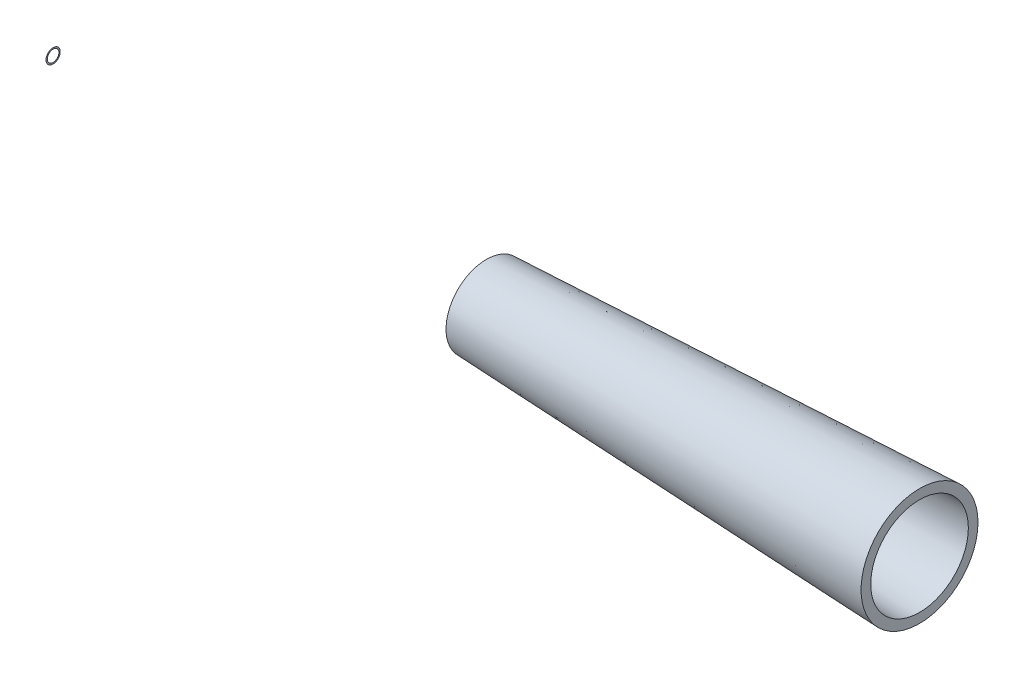
SolidWorks part; units mm, degrees
note: '?' marks a value the reader was unsure of.
ref_plane "Front Plane" through (0, 0, 0) normal (0, 0, 1) x (1, 0, 0)
ref_plane "Top Plane" through (0, 0, 0) normal (0, 1, 0) x (1, 0, 0)
ref_plane "Right Plane" through (0, 0, 0) normal (1, 0, 0) x (0, 0, -1)
sketch "Sketch2" plane through (0, 0, 0) normal (0, 0, 1) x (1, 0, 0)
  line L0 (-19.2758, 0) -> (50, 0) construction
  line L1 (0, 21.4747) -> (0, -15.9358) construction
  line L2 (0, 1.2) -> (54.9325, 5.0413) construction
  line L3 (0, 3.2) -> (55.9028, 7.1091) construction
  line L4 (0, 1.2) -> (50, 4.6963)
  line L5 (1.8511, 3.3294) -> (50, 6.6963)
  line L6 (50, 0) -> (50, 20.2328) construction
  line L7 (50, 6.6963) -> (50, 4.6963)
  arc A0 (0, 1.2) -> (1.8511, 3.3294) centre (1.9903, 1.3392) cw
  dimension "D1" = 4
  dimension "D2" = 1.2
  dimension "D3" = 2
  dimension "D4" = 50
revolve "Revolve2" add sketch "Sketch2" angle 360 about L0
ref_plane "Plane1" through (50, 0, 0) normal (1, 0, 0) x (0, 0, -1)
ref_axis "Axis1" through (50, 0, 0) along (-1, 0, 0)
sketch "Sketch3" plane through (0, 0, 0) normal (0, 0, 1) x (1, 0, 0)
  line L0 (50, 6.6963) -> (180, 6.6963) construction
  line L1 (50, -7.366) -> (50, 7.366) construction
  line L2 (50, 6.6963) -> (1.8511, 3.3294) construction
  line L3 (50, 6.6963) -> (180, 12.145) construction
  line L4 (50, 4.6946) -> (180, 10.1432)
  line L5 (180, 10.1432) -> (180, 12.145)
  line L6 (180, 12.145) -> (50, 6.6963)
  line L7 (50, 6.6963) -> (50, 4.6946)
  dimension "D1" = 2.4
  dimension "D2" = 130
  dimension "D3" = 2
revolve "Revolve3" add sketch "Sketch3" angle 360 about axis through (50, 0, 0) along (-1, 0, 0)
ref_plane "Plane2" through (90, 0, 0) normal (1, 0, 0) x (0, 0, -1)
ref_plane "Plane3" through (180, 0, 0) normal (1, 0, 0) x (0, 0, -1)
ref_plane "Plane4" through (0, -12.145, 0) normal (0, 1, 0) x (1, 0, 0)
ref_axis "Axis2" through (180, -12.145, -13.3595) along (0, 0, 1)?
ref_plane "Plane5" through (83.9275, 83.9275, 0) normal (-0.7071, -0.7071, 0) x (0, 0, 1)
ref_plane "Plane6" through (0, 0, 0) normal (1, 0, 0) x (0, 0, -1)
other "SurfaceCut9" flip cut yes
other "SurfaceCut12"
